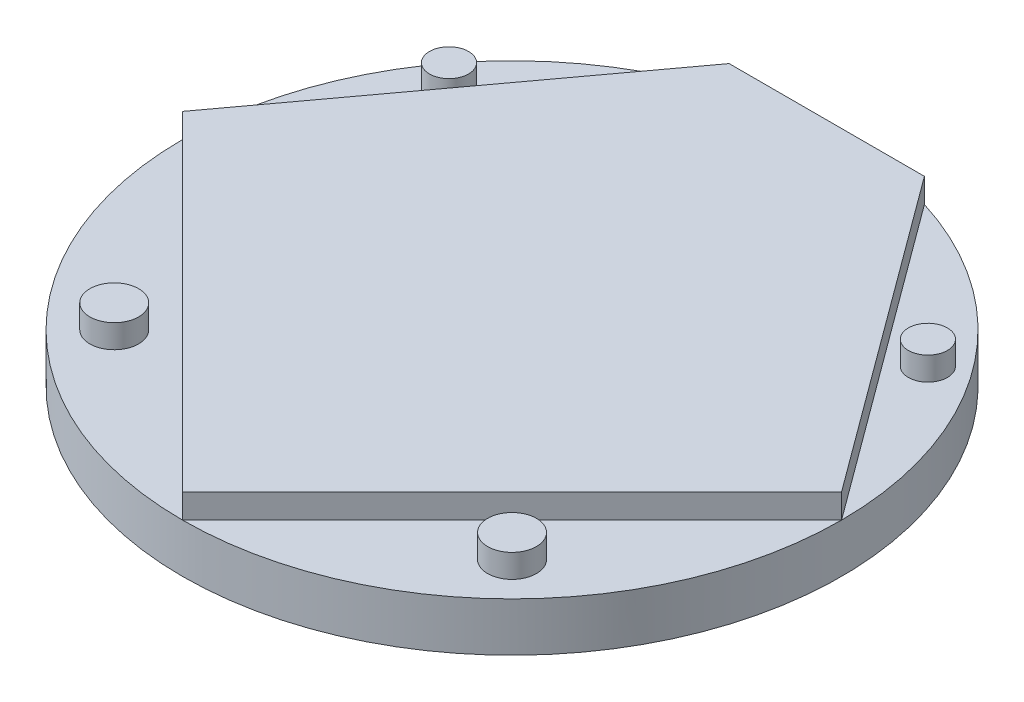
SolidWorks part; units mm, degrees
ref_plane "Front Plane" through (0, 0, 0) normal (0, 0, 1) x (1, 0, 0)
ref_plane "Top Plane" through (0, 0, 0) normal (0, 1, 0) x (1, 0, 0)
ref_plane "Right Plane" through (0, 0, 0) normal (1, 0, 0) x (0, 0, -1)
sketch "Sketch1" plane through (0, 0, 0) normal (0, 1, 0) x (1, 0, 0)
  circle A0 centre (0, 0) radius 85.725
extrude "Boss-Extrude1" add sketch "Sketch1" along normal blind 12.7
sketch "Sketch2" plane through (0, 12.7, 0) normal (0, 1, 0) x (1, 0, 0)
  line L0 (0, 0) -> (0, 85.725) construction
  line L1 (0, 0) -> (-85.725, 0) construction
  line L2 (-85.725, 0) -> (85.725, 0) construction
  line L3 (-25.4, 81.8756) -> (25.4, 81.8756)
  line L5 (-25.4, 81.8756) -> (-85.725, 0)
  line L6 (-85.725, 0) -> (0, -85.725)
  line L7 (0, -85.725) -> (85.725, 0)
  line L8 (85.725, 0) -> (25.4, 81.8756)
  circle A0 centre (0, 0) radius 85.725 construction
  dimension "D1" = 50.8
extrude "Boss-Extrude2" add sketch "Sketch2" along normal blind 6.35
sketch "Sketch3" plane through (0, 12.7, 0) normal (0, 1, 0) x (1, 0, 0)
  line L0 (-42.8625, -42.8625) -> (-60.6167, -60.6167) construction
  line L1 (-85.725, 0) -> (0, -85.725) construction
  line L2 (60.6167, -60.6167) -> (42.8625, -42.8625) construction
  line L3 (0, -85.725) -> (85.725, 0) construction
  line L4 (55.5625, 40.9378) -> (69.0152, 50.8496) construction
  line L5 (85.725, 0) -> (25.4, 81.8756) construction
  line L6 (-69.0152, 50.8496) -> (-55.5625, 40.9378) construction
  line L7 (-25.4, 81.8756) -> (-85.725, 0) construction
  circle A0 centre (-51.7396, -51.7396) radius 6.35
  arc A1 (-85.725, 0) -> (0, -85.725) centre (0, 0) ccw construction
  circle A2 centre (51.7396, -51.7396) radius 6.35
  arc A3 (0, -85.725) -> (85.725, 0) centre (0, 0) ccw construction
  circle A4 centre (62.2888, 45.8937) radius 5.08
  arc A5 (85.725, 0) -> (25.4, 81.8756) centre (0, 0) ccw construction
  arc A6 (-25.4, 81.8756) -> (-85.725, 0) centre (0, 0) ccw construction
  circle A7 centre (-62.2888, 45.8937) radius 5.08
  dimension "D1" = 12.7
  dimension "D2" = 10.16
extrude "Boss-Extrude3" add sketch "Sketch3" along normal blind 6.096
